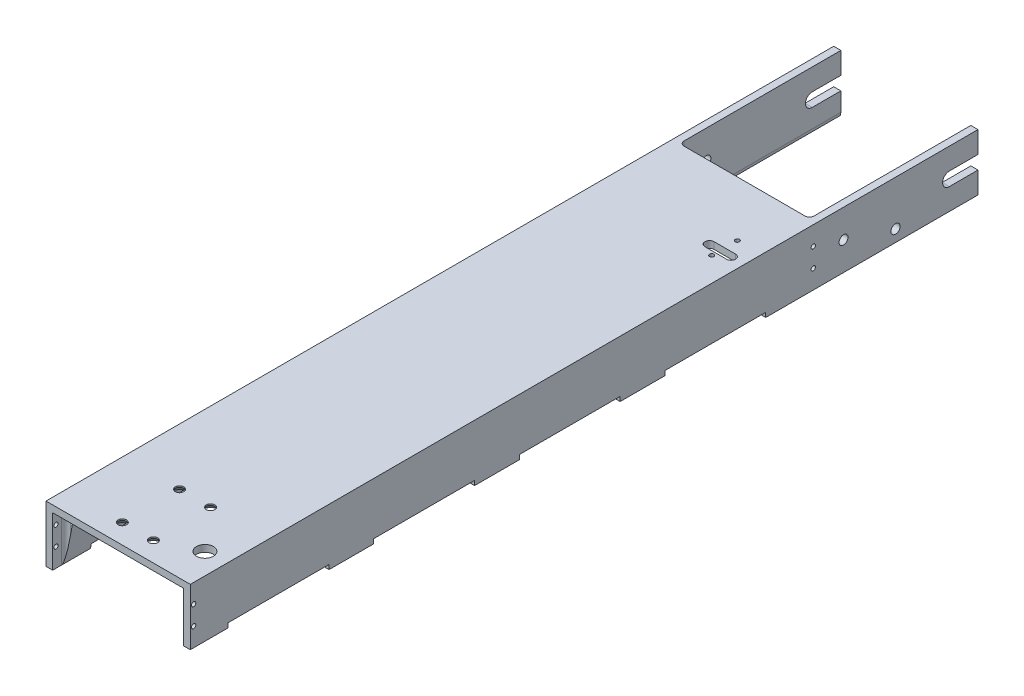
SolidWorks part; units mm, degrees
ref_plane "Front Plane" through (0, 0, 0) normal (0, 0, 1) x (1, 0, 0)
ref_plane "Top Plane" through (0, 0, 0) normal (0, 1, 0) x (1, 0, 0)
ref_plane "Right Plane" through (0, 0, 0) normal (1, 0, 0) x (0, 0, -1)
sketch "Sketch1" plane through (0, 0, 0) normal (0, 0, 1) x (1, 0, 0)
  line L0 (-51.1048, 0) -> (51.1048, 0)
  line L1 (51.1048, 0) -> (51.1048, -40.132)
  line L2 (51.1048, -40.132) -> (46.4058, -40.132)
  line L3 (46.4058, -40.132) -> (41.2191, -10.0709)
  line L4 (34.9616, -4.8006) -> (-34.9616, -4.8006)
  line L5 (-41.2191, -10.0709) -> (-46.4058, -40.132)
  line L6 (-46.4058, -40.132) -> (-51.1048, -40.132)
  line L7 (-51.1048, -40.132) -> (-51.1048, 0)
  arc A0 (-34.9616, -4.8006) -> (-41.2191, -10.0709) centre (-34.9616, -11.1506) ccw
  arc A1 (41.2191, -10.0709) -> (34.9616, -4.8006) centre (34.9616, -11.1506) ccw
  point P8 (0, 0)
  point P12 (-40.3098, -4.8006)
  point P15 (40.3098, -4.8006)
  dimension "D7" = 6.35
  dimension "D1" = 40.132
  dimension "D2" = 4.699
  dimension "D3" = 4.8006
  dimension "D4" = 102.2096
  dimension "D5" = 10.795
  dimension "D6" = 10.795
extrude "Boss-Extrude1" add sketch "Sketch1" along normal blind 558.0063
sketch "Sketch3" plane through (0, 0, 0) normal (0, 1, 0) x (1, 0, 0)
  line L0 (51.1048, 0) -> (-51.1048, 0) construction
  line L1 (-42.8625, -114.3) -> (42.8625, -114.3)
  line L2 (-46.0375, -111.125) -> (-46.0375, 0)
  line L3 (-46.0375, 0) -> (46.0375, 0)
  line L4 (46.0375, -111.125) -> (46.0375, 0)
  line L5 (-46.0375, -114.3) -> (46.0375, 0) construction
  line L6 (-46.0375, 0) -> (46.0375, -114.3) construction
  line L7 (-34.9616, -558.0063) -> (34.9616, -558.0063) construction
  line L9 (26.3398, -165.4336) -> (41.5798, -165.4336) construction
  line L10 (26.3398, -162.2586) -> (41.5798, -162.2586)
  line L11 (26.3398, -168.6086) -> (41.5798, -168.6086)
  line L12 (0, -1000) -> (0, 49000) construction
  line L13 (51.1048, -558.0063) -> (-51.1048, -558.0063) construction
  line L15 (51.1048, -558.0063) -> (51.1048, 0) construction
  line L16 (-46.0375, -161.1156) -> (46.0375, -161.1156) construction
  arc A0 (26.3398, -162.2586) -> (26.3398, -168.6086) centre (26.3398, -165.4336) ccw
  arc A1 (41.5798, -168.6086) -> (41.5798, -162.2586) centre (41.5798, -165.4336) ccw
  circle A2 centre (33.9598, -153.3686) radius 1.524
  circle A3 centre (33.9598, -171.5296) radius 1.524
  circle A4 centre (-11.0109, -544.0362) radius 3
  circle A5 centre (11.0109, -503.5232) radius 3
  circle A6 centre (-11.0109, -503.5232) radius 3
  circle A7 centre (11.0109, -544.0362) radius 3
  circle A8 centre (36.0486, -532.6063) radius 6
  arc A9 (-42.8625, -114.3) -> (-46.0375, -111.125) centre (-42.8625, -111.125) cw
  arc A10 (42.8625, -114.3) -> (46.0375, -111.125) centre (42.8625, -111.125) ccw
  point P0 (0, -57.15)
  point P13 (33.9598, -165.4336)
  dimension "D2" = 6.35
  dimension "D6" = 3.048
  dimension "D9" = 6
  dimension "D13" = 12
  dimension "D17" = 3.175
  dimension "D1" = 114.3
  dimension "D3" = 15.24
  dimension "D4" = 9.525
  dimension "D5" = 1.143
  dimension "D7" = 2.921
  dimension "D8" = 8.89
  dimension "D10" = 40.513
  dimension "D11" = 22.0218
  dimension "D12" = 13.97
  dimension "D14" = 15.0562
  dimension "D15" = 25.4
  dimension "D16" = 92.075
extrude "Cut-Extrude1" cut sketch "Sketch3" against normal through all
sketch "Sketch4" plane through (51.1048, 0, 0) normal (1, 0, 0) x (0, 0, -1)
  line L0 (5.08, -20.066) -> (-20.32, -20.066) construction
  line L1 (5.08, -24.8285) -> (-20.32, -24.8285)
  line L2 (5.08, -15.3035) -> (-20.32, -15.3035)
  line L3 (0, -40.132) -> (0, 0) construction
  line L4 (-150.368, -40.132) -> (-150.368, -36.957)
  line L5 (-558.0063, -40.132) -> (0, -40.132) construction
  line L6 (-150.368, -36.957) -> (-221.8055, -36.957)
  line L7 (-221.8055, -36.957) -> (-221.8055, -40.132)
  line L8 (-221.8055, -40.132) -> (-150.368, -40.132)
  line L9 (-156.3531, 0) -> (-111.9031, 0) construction
  line L10 (0, 0) -> (0, -40.132) construction
  line L11 (-558.0063, -40.132) -> (-558.0063, 0) construction
  line L12 (-558.0063, 0) -> (0, 0) construction
  line L21 (-253.492, -40.132) -> (-253.492, -36.957)
  line L22 (-253.492, -36.957) -> (-324.9295, -36.957)
  line L23 (-324.9295, -36.957) -> (-324.9295, -40.132)
  line L24 (-324.9295, -40.132) -> (-253.492, -40.132)
  line L25 (-356.616, -40.132) -> (-356.616, -36.957)
  line L26 (-356.616, -36.957) -> (-428.0535, -36.957)
  line L27 (-428.0535, -36.957) -> (-428.0535, -40.132)
  line L28 (-428.0535, -40.132) -> (-356.616, -40.132)
  line L29 (-459.74, -40.132) -> (-459.74, -36.957)
  line L30 (-459.74, -36.957) -> (-531.1775, -36.957)
  line L31 (-531.1775, -36.957) -> (-531.1775, -40.132)
  line L32 (-531.1775, -40.132) -> (-459.74, -40.132)
  arc A0 (5.08, -24.8285) -> (5.08, -15.3035) centre (5.08, -20.066) ccw
  arc A1 (-20.32, -15.3035) -> (-20.32, -24.8285) centre (-20.32, -20.066) ccw
  circle A2 centre (-95.25, -20.066) radius 3.175
  circle A3 centre (-116.6813, -26.8224) radius 1.524
  circle A4 centre (-116.6812, -13.4112) radius 1.524
  circle A5 centre (-555.625, -13.4112) radius 1.524
  circle A6 centre (-555.625, -26.8224) radius 1.524
  point P3 (-7.62, -20.066)
  point P10 (0, -20.066)
  point P44 (0, -20.066)
  dimension "D3" = 9.525
  dimension "D5" = 6.35
  dimension "D10" = 3.048
  dimension "D14" = 3.048
  dimension "D1" = 25.4
  dimension "D2" = 20.32
  dimension "D4" = 95.25
  dimension "D6" = 3.175
  dimension "D7" = 71.4375
  dimension "D8" = 150.368
  dimension "D11" = 13.4112
  dimension "D12" = 13.4112
  dimension "D13" = 116.6813
  dimension "D15" = 2.3813
  dimension "D16" = 13.4112
  dimension "D17" = 13.4112
  dimension "D9" = 4
extrude "Cut-Extrude2" cut sketch "Sketch4" against normal through all
chamfer "Chamfer1" distance 3.8862 angle 42 4 edges at (8.0109, -4.8006, 503.5232) (8.0109, -4.8006, 544.0362) (-14.0109, -4.8006, 544.0362) (-14.0109, -4.8006, 503.5232) first distance on face at (14.0109, 0, 503.5232) first distance on face at (14.0109, 0, 544.0362) first distance on face at (-14.0109, 0, 544.0362) first distance on face at (-14.0109, 0, 503.5232)
sketch "Sketch5" plane through (0, -40.132, 0) normal (0, -1, 0) x (1, 0, 0)
  line L0 (-51.1048, 150.368) -> (-51.1048, 221.8055) construction
  line L1 (31.3779, 146.05) -> (42.5958, 146.05)
  line L2 (31.3779, 146.05) -> (31.3779, 177.8)
  line L3 (31.3779, 177.8) -> (42.5958, 177.8)
  line L4 (46.4058, 149.86) -> (46.4058, 173.99)
  line L5 (31.3779, 146.05) -> (46.4058, 177.8) construction
  line L6 (31.3779, 177.8) -> (46.4058, 146.05) construction
  line L7 (46.4058, 558.0063) -> (46.4058, 531.1775) construction
  line L8 (-56.5438, 388.0168) -> (-40.0893, 388.0168) construction
  line L9 (51.1048, 150.368) -> (51.1048, 221.8055) construction
  line L10 (-42.2275, 221.0689) -> (-29.5583, 221.0689)
  line L11 (-46.0375, 217.2589) -> (-46.0375, 102.0788)
  line L12 (-42.2275, 98.2688) -> (-29.5583, 98.2688)
  line L13 (-29.5583, 221.0689) -> (-29.5583, 98.2688)
  line L16 (-41.9227, 217.2589) -> (10.0965, 217.2589) construction
  line L19 (46.4058, 558.0063) -> (32.5205, 558.0063)
  line L20 (46.4058, 558.0063) -> (46.4058, 513.5563)
  line L21 (43.2308, 510.3813) -> (32.5205, 510.3813)
  line L22 (32.5205, 558.0063) -> (32.5205, 510.3813)
  line L24 (-46.4058, 558.0063) -> (-34.8231, 558.0063)
  line L25 (-46.4058, 558.0063) -> (-46.4058, 551.6563)
  line L26 (-43.2308, 548.4813) -> (-34.8231, 548.4813)
  line L27 (-34.8231, 558.0063) -> (-34.8231, 548.4813)
  line L28 (42.8625, 123.825) -> (32.685, 123.825)
  line L29 (46.0375, 120.65) -> (46.0375, 102.6149)
  line L30 (46.0375, 102.6149) -> (32.685, 102.6149)
  line L31 (32.685, 123.825) -> (32.685, 102.6149)
  line L33 (-46.0375, 0) -> (-46.0375, 111.125) construction
  line L34 (46.0375, 111.125) -> (46.0375, 0) construction
  arc A0 (42.5958, 177.8) -> (46.4058, 173.99) centre (42.5958, 173.99) cw
  arc A1 (42.5958, 146.05) -> (46.4058, 149.86) centre (42.5958, 149.86) ccw
  arc A2 (-46.0375, 102.0788) -> (-42.2275, 98.2688) centre (-42.2275, 102.0788) ccw
  arc A3 (-42.2275, 221.0689) -> (-46.0375, 217.2589) centre (-42.2275, 217.2589) ccw
  arc A4 (46.4058, 513.5563) -> (43.2308, 510.3813) centre (43.2308, 513.5563) cw
  arc A5 (-46.4058, 551.6563) -> (-43.2308, 548.4813) centre (-43.2308, 551.6563) ccw
  arc A6 (42.8625, 123.825) -> (46.0375, 120.65) centre (42.8625, 120.65) cw
  circle A7 centre (-48.7235, 186.0867) radius 1.1303
  circle A8 centre (-48.7236, 284.8928) radius 1.1303
  circle A9 centre (-48.7236, 391.1918) radius 1.1303
  circle A10 centre (-48.7236, 491.7745) radius 1.1303
  circle A11 centre (48.7236, 186.0867) radius 1.1303
  circle A15 centre (48.7235, 289.9728) radius 1.1303
  circle A16 centre (48.7235, 393.8587) radius 1.1303
  circle A17 centre (48.7235, 497.7447) radius 1.1303
  point P0 (38.8919, 161.925)
  point P16 (-51.1048, 186.0867)
  point P55 (46.4058, 123.825)
  point P58 (51.1048, 186.0867)
  dimension "D3" = 3.81
  dimension "D4" = 3.175
  dimension "D6" = 3.175
  dimension "D7" = 3.175
  dimension "D9" = 2.2606
  dimension "D13" = 2.2606
  dimension "D1" = 31.75
  dimension "D2" = 146.05
  dimension "D5" = 44.45
  dimension "D8" = 6.35
  dimension "D10" = 2.3813
  dimension "D12" = 2.3813
  dimension "D11" = 3.175
  dimension "D14" = 4
extrude "Cut-Extrude3" cut sketch "Sketch5" against normal up to surface (35.3314 mm away) up to face at (4.5117, -4.8006, 503.5232)
sketch "Sketch6" plane through (-51.1048, 0, 0) normal (-1, 0, 0) x (0, 0, 1)
  line L0 (558.0063, 0) -> (558.0063, -40.132) construction
  line L1 (402.4313, -25.4) -> (446.8813, -25.4)
  line L2 (399.2563, -22.225) -> (399.2563, -15.875)
  line L3 (402.4313, -12.7) -> (446.8813, -12.7)
  line L4 (450.0563, -22.225) -> (450.0563, -15.875)
  line L5 (558.0063, 0) -> (0, 0) construction
  circle A0 centre (200.8251, -23.3045) radius 1.5494
  circle A1 centre (162.7759, -23.3045) radius 1.5494
  circle A2 centre (136.6393, -23.3045) radius 1.5494
  circle A3 centre (396.0813, -9.525) radius 1.1303
  circle A4 centre (162.7759, -23.3045) radius 1.27 construction
  circle A5 centre (136.6393, -23.3045) radius 1.27 construction
  circle A6 centre (200.8251, -23.3045) radius 1.27 construction
  circle A7 centre (453.2313, -9.525) radius 1.1303
  circle A8 centre (453.2313, -28.575) radius 1.1303
  circle A9 centre (396.0813, -28.575) radius 1.1303
  arc A10 (446.8813, -12.7) -> (450.0563, -15.875) centre (446.8813, -15.875) cw
  arc A11 (446.8813, -25.4) -> (450.0563, -22.225) centre (446.8813, -22.225) ccw
  arc A12 (402.4313, -25.4) -> (399.2563, -22.225) centre (402.4313, -22.225) cw
  arc A13 (399.2563, -15.875) -> (402.4313, -12.7) centre (402.4313, -15.875) cw
  point P30 (450.0563, -12.7)
  point P35 (399.2563, -25.4)
  point P38 (399.2563, -12.7)
  dimension "D1" = 3.0988
  dimension "D6" = 2.2606
  dimension "D11" = 3.175
  dimension "D2" = 107.95
  dimension "D3" = 50.8
  dimension "D4" = 12.7
  dimension "D5" = 12.7
  dimension "D7" = 3.175
  dimension "D8" = 3.175
  dimension "D9" = 3.175
  dimension "D10" = 3.175
extrude "Cut-Extrude7" cut sketch "Sketch6" against normal up to next
sketch "Sketch7" plane through (51.1048, 0, 0) normal (1, 0, 0) x (0, 0, -1)
  line L0 (0, -40.132) -> (0, -24.8285) construction
  line L1 (-150.368, -40.132) -> (0, -40.132) construction
  circle A0 centre (-58.42, -31.75) radius 3.2512
  dimension "D3" = 6.5024
  dimension "D1" = 58.42
  dimension "D2" = 8.382
extrude "Cut-Extrude8" cut sketch "Sketch7" against normal up to next
